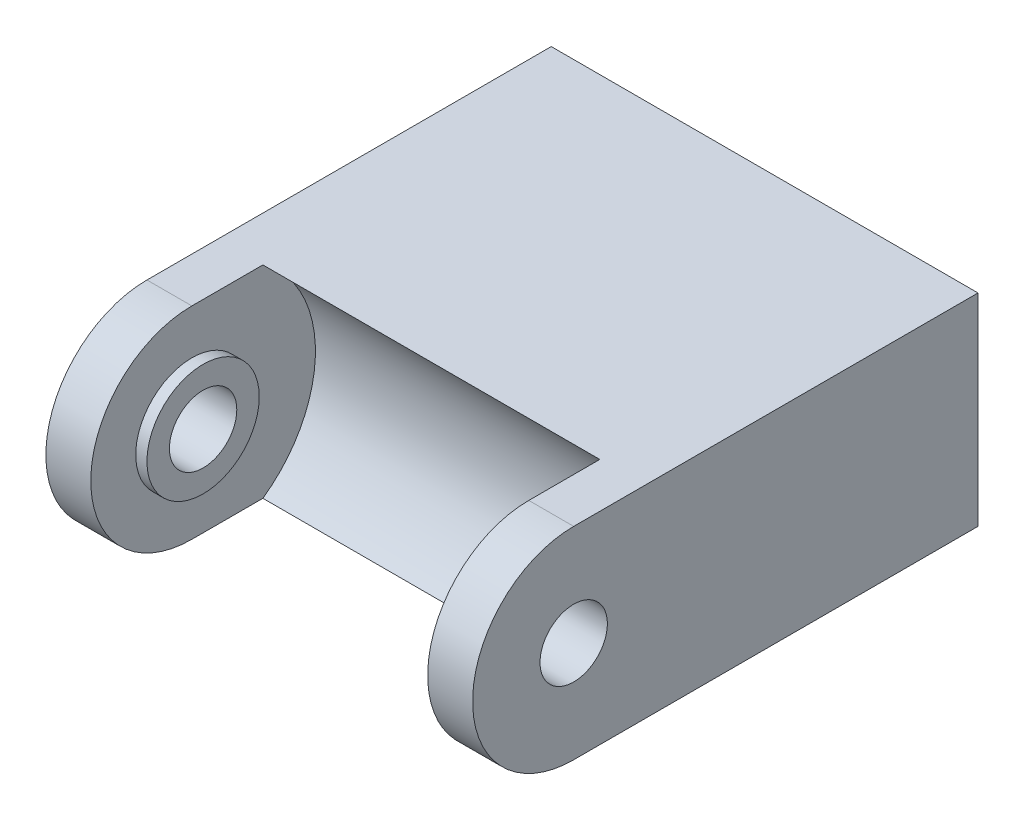
SolidWorks part; units mm, degrees
ref_plane "Front" through (0, 0, 0) normal (0, 0, 1) x (1, 0, 0)
ref_plane "Top" through (0, 0, 0) normal (0, 1, 0) x (1, 0, 0)
ref_plane "Right" through (0, 0, 0) normal (1, 0, 0) x (0, 0, -1)
sketch "Эскиз1" plane through (0, 0, 0) normal (1, 0, 0) x (0, 0, -1)
  line L0 (0, 4.5) -> (18, 4.5)
  line L1 (18, 4.5) -> (18, -4.5)
  line L2 (18, -4.5) -> (0, -4.5)
  circle A0 centre (0, 0) radius 4.5
  dimension "D1" = 9
  dimension "D2" = 18
extrude "Бобышка-Вытянуть1" add sketch "Эскиз1" along normal blind 9.5 and the other way blind 9.5 contours A0 | A0 L2 L1 L0 region at (0, 0, -10.7323) region at (0, 0, 0)
sketch "Эскиз2" plane through (0, 0, 0) normal (1, 0, 0) x (0, 0, -1)
  circle A0 centre (0, 0) radius 5.5
extrude "Вырез-Вытянуть1" cut sketch "Эскиз2" against normal blind 7 and the other way blind 7
sketch "Эскиз3" plane through (0, 0, 0) normal (1, 0, 0) x (0, 0, -1)
  circle A0 centre (0, 0) radius 1.5
extrude "Вырез-Вытянуть2" cut sketch "Эскиз3" against normal through all both and the other way through all
sketch "Эскиз4" plane through (0, 0, 0) normal (1, 0, 0) x (0, 0, -1)
  circle A0 centre (0, 0) radius 5.5
  circle A1 centre (0, 0) radius 2.5
  dimension "D1" = 5
  dimension "D2" = 11
extrude "Вырез-Вытянуть3" cut sketch "Эскиз4" against normal blind 7.5 and the other way blind 7.5
sketch "Эскиз5" plane through (0, 0, -18) normal (0, 0, -1) x (-1, 0, 0)
  circle A0 centre (0, 0) radius 1.75
extrude "Вырез-Вытянуть4" cut sketch "Эскиз5" against normal blind 2
